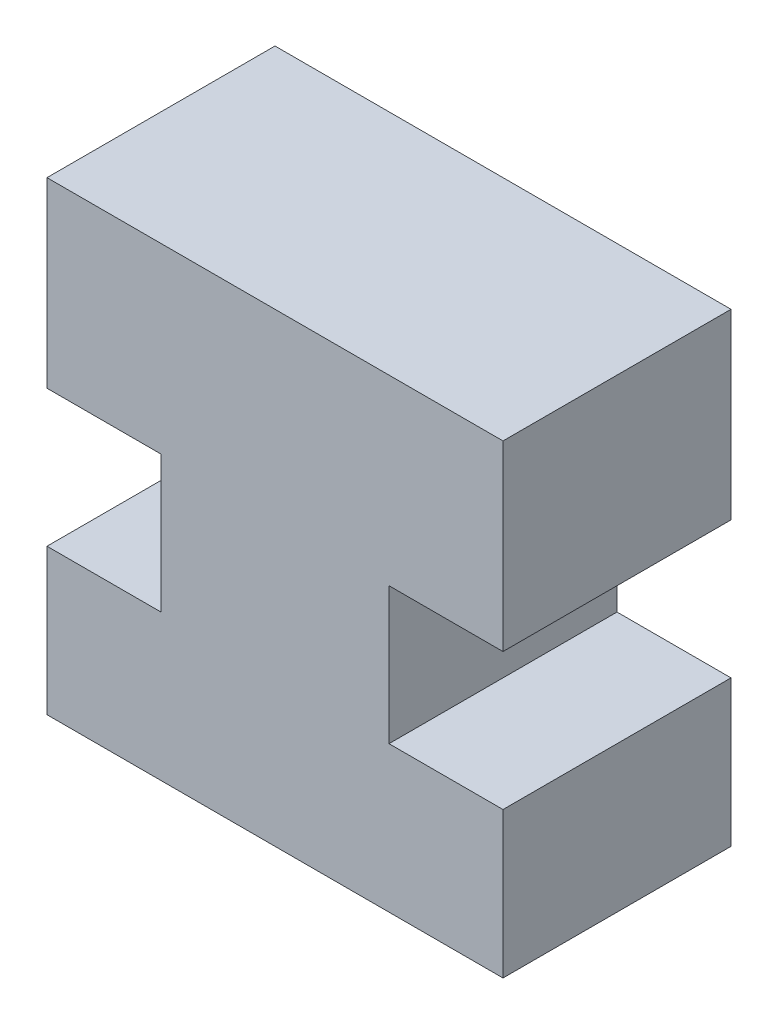
SolidWorks part; units mm, degrees
ref_plane "Front Plane" through (0, 0, 0) normal (0, 0, 1) x (1, 0, 0)
ref_plane "Top Plane" through (0, 0, 0) normal (0, 1, 0) x (1, 0, 0)
ref_plane "Right Plane" through (0, 0, 0) normal (1, 0, 0) x (0, 0, -1)
sketch "Sketch2" plane through (0, 0, 0) normal (0, 0, 1) x (1, 0, 0)
  line L0 (0, 0) -> (12.7, 0)
  line L1 (12.7, 0) -> (12.7, -5.08)
  line L2 (12.7, -5.08) -> (9.525, -5.08)
  line L3 (9.525, -5.08) -> (9.525, -8.89)
  line L4 (9.525, -8.89) -> (12.7, -8.89)
  line L5 (12.7, -8.89) -> (12.7, -12.954)
  line L6 (12.7, -12.954) -> (0, -12.954)
  line L7 (0, -12.954) -> (0, -8.89)
  line L8 (0, -8.89) -> (3.175, -8.89)
  line L9 (3.175, -8.89) -> (3.175, -5.08)
  line L10 (3.175, -5.08) -> (0, -5.08)
  line L11 (0, -5.08) -> (0, 0)
  dimension "D1" = 12.7
  dimension "D2" = 12.7
  dimension "D3" = 5.08
  dimension "D4" = 3.81
  dimension "D5" = 5.08
  dimension "D6" = 3.81
  dimension "D7" = 7.874
  dimension "D8" = 3.175
  dimension "D9" = 3.175
extrude "body" add sketch "Sketch2" along normal blind 6.35
ref_point "Point1"
sketch "Sketch4" plane through (0, -12.954, 0) normal (0, -1, 0) x (1, 0, 0)
  circle A0 centre (6.35, 3.175) radius 1.27
extrude "flag" add sketch "Sketch4" along normal blind 0.254
fillet "holder" radius 2.54 1 edges at (6.35, -12.954, 4.445)
